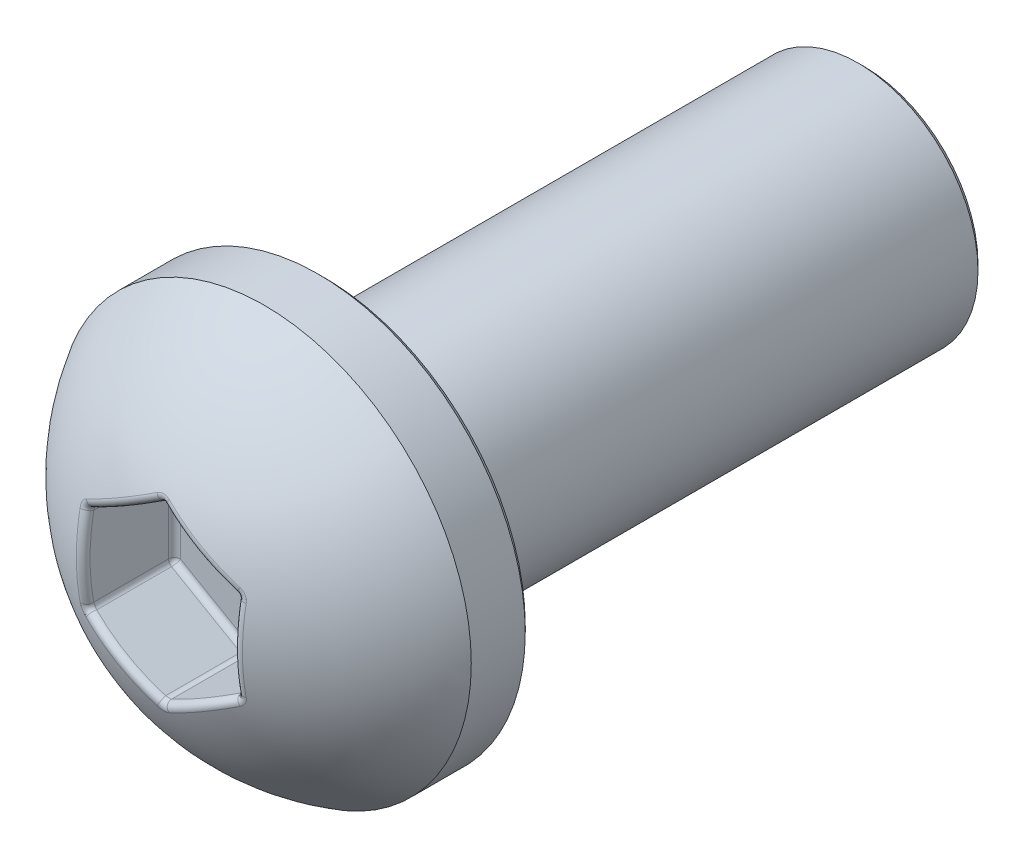
SolidWorks part; units mm, degrees
material "1.4000 (X6Cr13)"
ref_plane "Ebene vorne" through (0, 0, 0) normal (0, 0, 1) x (1, 0, 0)
ref_plane "Ebene oben" through (0, 0, 0) normal (0, 1, 0) x (1, 0, 0)
ref_plane "Ebene rechts" through (0, 0, 0) normal (1, 0, 0) x (0, 0, -1)
sketch "Skizze1" plane through (0, 0, 0) normal (1, 0, 0) x (0, 0, -1)
  line L0 (-21.9199, 0) -> (33.7608, 0) construction
  line L1 (0, 13.9907) -> (0, -9.4798) construction
  line L3 (-2, 6.9) -> (0, 6.9)
  line L4 (0, 6.9) -> (0, 4)
  line L5 (0, 4) -> (18, 4)
  line L6 (18, 4) -> (18, 0)
  line L7 (18, 0) -> (-6, 0)
  arc A0 (-2, 6.9) -> (-6, 0) centre (1.9513, 0) ccw
  dimension "D5" = 2
  dimension "D1" = 8
  dimension "D2" = 6
  dimension "D3" = 13.8
  dimension "D4" = 18
revolve "Rotation1" add sketch "Skizze1" angle 360 about L0
ref_plane "Ebene1" through (0, 0, 6) normal (0, 0, 1) x (1, 0, 0)
sketch "Skizze2" plane through (0, 0, 6) normal (0, 0, 1) x (1, 0, 0)
  line L0 (0, 8.6995) -> (0, -7.3778) construction
  line L1 (2.5, -1.4434) -> (2.5, 1.4434)
  line L2 (2.5, 1.4434) -> (0, 2.8868)
  line L3 (0, 2.8868) -> (-2.5, 1.4434)
  line L4 (-2.5, 1.4434) -> (-2.5, -1.4434)
  line L5 (-2.5, -1.4434) -> (0, -2.8868)
  line L6 (0, -2.8868) -> (2.5, -1.4434)
  circle A0 centre (0, 0) radius 2.5 construction
  dimension "D1" = 5
extrude "Schnitt-Linear austragen1" cut sketch "Skizze2" against normal blind 3.5
chamfer "Fase1" distance 0.2 angle 45 2 edges at (6.9, 0, 0) (4, 0, -18)
fillet "Verrundung1" radius 0.2 19 edges at (-1.25, -2.1651, 2.5) (-2.5, 0, 2.5) (-1.25, 2.1651, 2.5) (1.25, 2.1651, 2.5) (2.5, 0, 2.5) (1.25, -2.1651, 2.5) (-2.5, -1.4434, 3.9787) (0, -2.8868, 3.9787) (2.5, -1.4434, 3.9787) (2.5, 1.4434, 3.9787) (0, 2.8868, 3.9787) (-2.5, 1.4434, 3.9787) (4, 0, 0) (-1.25, -2.1651, 5.5968) (-2.5, 0, 5.5968) (1.25, -2.1651, 5.5968) (-1.25, 2.1651, 5.5968) (2.5, 0, 5.5968) (1.25, 2.1651, 5.5968)
ref_axis "Achse1" through (0, 0, -19.6323) along (0, 0, 1)
